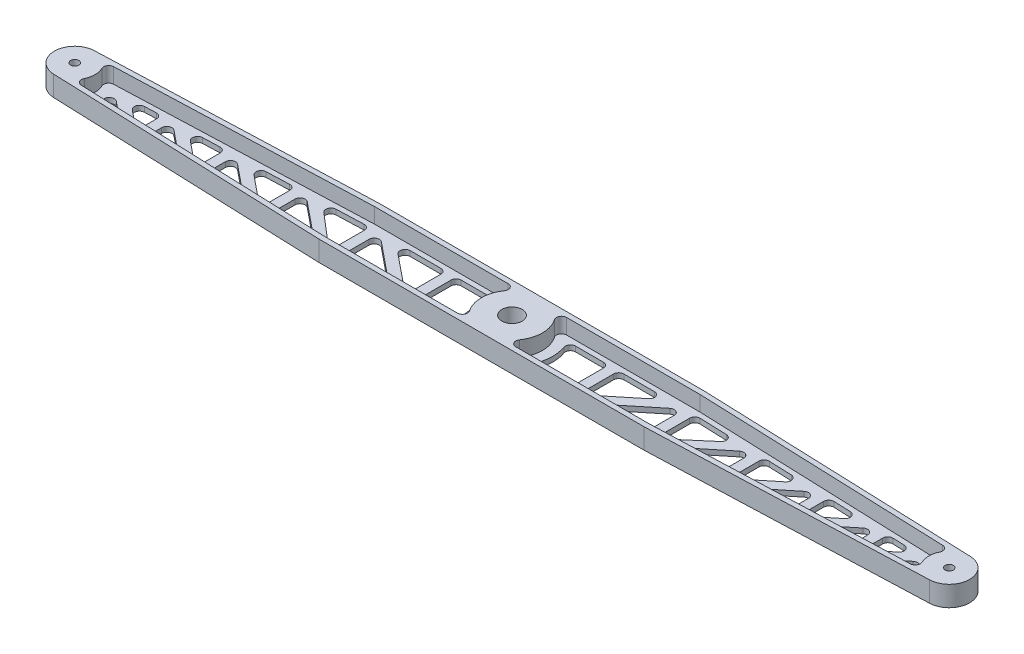
SolidWorks part; units mm, degrees
material "6061 Alloy"
ref_plane "Front Plane" through (0, 0, 0) normal (0, 0, 1) x (1, 0, 0)
ref_plane "Top Plane" through (0, 0, 0) normal (0, 1, 0) x (1, 0, 0)
ref_plane "Right Plane" through (0, 0, 0) normal (1, 0, 0) x (0, 0, -1)
sketch "Sketch1" plane through (0, 0, 0) normal (1, 0, 0) x (0, 0, -1)
  line L1 (-19.05, -6.35) -> (19.05, -6.35)
  line L2 (-19.05, -6.35) -> (-19.05, 6.35)
  line L3 (-19.05, 6.35) -> (19.05, 6.35)
  line L4 (19.05, -6.35) -> (19.05, 6.35)
  line L5 (-19.05, -6.35) -> (19.05, 6.35) construction
  line L6 (-19.05, 6.35) -> (19.05, -6.35) construction
  point P0 (0, 0)
  dimension "D1" = 38.1
  dimension "D2" = 12.7
extrude "Boss-Extrude1" add sketch "Sketch1" along normal mid plane 584.2
sketch "Sketch2" plane through (0, 6.35, 0) normal (0, 1, 0) x (1, 0, 0)
  circle A0 centre (0, 0) radius 6.35
  dimension "D1" = 12.7
extrude "Pivot Hole" cut sketch "Sketch2" against normal through all
hole_wizard "End Holes" positions "Sketch4" profile "Sketch3" tap size "1/4-20" standard "ANSI Inch" end condition through all
sketch "Sketch4" plane through (0, -6.35, 0) normal (0, -1, 0) x (-1, 0, 0)
  line L0 (273.05, 0) -> (292.1, 0) construction
  line L1 (292.1, -19.05) -> (292.1, 19.05) construction
  line L4 (-273.05, 0) -> (-292.1, 0) construction
  line L5 (-292.1, -19.05) -> (-292.1, 19.05) construction
  point P0 (273.05, 0)
  point P2 (-273.05, 0)
  dimension "D1" = 19.05
sketch "Sketch3" plane through (-273.05, -6.35, 0) normal (1, 0, 0) x (0, 0, -1)
  line L0 (0, 0) -> (0, 12.7)
  line L1 (0, 12.7) -> (2.5527, 12.7)
  line L2 (2.5527, 12.7) -> (2.5527, 0)
  line L5 (2.5527, 0) -> (0, 0)
  line L11 (0, -6.35) -> (0, 107.95) construction
  dimension "Thread Major Dia." = 5.1054
  dimension "Thru Tap Drill Depth" = 12.7
sketch "Sketch7" plane through (0, 6.35, 0) normal (0, 1, 0) x (1, 0, 0)
  line L0 (101.6, 19.05) -> (-101.6, 19.05)
  line L1 (292.1, 19.05) -> (-292.1, 19.05) construction
  line L2 (-101.6, 19.05) -> (-273.5194, 12.6913)
  line L3 (-273.5194, -12.6913) -> (-101.6, -19.05)
  line L4 (292.1, -19.05) -> (-292.1, -19.05) construction
  line L5 (-101.6, -19.05) -> (101.6, -19.05)
  line L6 (0, 19.05) -> (0, -19.05) construction
  line L7 (273.5194, -12.6913) -> (101.6, -19.05)
  line L8 (101.6, 19.05) -> (273.5194, 12.6913)
  line L13 (-292.1, 19.05) -> (-292.1, -19.05)
  line L14 (-292.1, -19.05) -> (292.1, -19.05)
  line L15 (292.1, -19.05) -> (292.1, 19.05)
  line L16 (292.1, 19.05) -> (-292.1, 19.05)
  line L17 (-292.1, 19.05) -> (-292.1, -19.05)
  line L18 (-292.1, -19.05) -> (292.1, -19.05)
  line L19 (292.1, -19.05) -> (292.1, 19.05)
  line L20 (292.1, 19.05) -> (-292.1, 19.05)
  arc A0 (-273.5194, 12.6913) -> (-273.5194, -12.6913) centre (-273.05, 0) ccw
  arc A1 (273.5194, 12.6913) -> (273.5194, -12.6913) centre (273.05, 0) cw
  line M4 (-292.1, 19.05) -> (-292.1, -19.05)
  line M5 (-292.1, -19.05) -> (292.1, -19.05)
  line M6 (292.1, -19.05) -> (292.1, 19.05)
  line M7 (292.1, 19.05) -> (-292.1, 19.05)
  dimension "D2" = 12.7
  dimension "D1" = 101.6
  dimension "D3" = 0
extrude "Cut-Extrude3" cut sketch "Sketch7" against normal up to next contours A0 L2 L3 M7 M4 M5 | L8 A1 L7 M5 M6 M7 region at (196.85, 6.35, -17.1073) region at (-187.6315, 6.35, -17.8121)
sketch "Sketch9" plane through (0, 6.35, 0) normal (0, 1, 0) x (1, 0, 0)
  line L0 (-265.0075, 9.829) -> (-101.6, 15.8728)
  line L1 (-101.6, 15.8728) -> (-10.5336, 15.8728)
  line L2 (-10.5336, -15.8728) -> (-101.6, -15.8728)
  line L3 (-101.6, -15.8728) -> (-265.0075, -9.829)
  line L4 (-273.5194, -12.6913) -> (-101.6, -19.05) construction
  line L5 (-101.6, 19.05) -> (-273.5194, 12.6913) construction
  line L6 (0, 0) -> (0, -19.05) construction
  line L7 (101.6, -19.05) -> (-101.6, -19.05) construction
  line L8 (101.6, -15.8728) -> (265.0075, -9.829)
  line L9 (10.5336, -15.8728) -> (101.6, -15.8728)
  line L10 (101.6, 15.8728) -> (10.5336, 15.8728)
  line L11 (265.0075, 9.829) -> (101.6, 15.8728)
  arc A0 (-265.0075, 9.829) -> (-265.0075, -9.829) centre (-273.05, 0) cw
  arc A1 (-273.5194, 12.6913) -> (-273.5194, -12.6913) centre (-273.05, 0) ccw construction
  arc A2 (-10.5336, 15.8728) -> (-10.5336, -15.8728) centre (0, 0) ccw
  arc A3 (10.5336, 15.8728) -> (10.5336, -15.8728) centre (0, 0) cw
  arc A4 (265.0075, 9.829) -> (265.0075, -9.829) centre (273.05, 0) ccw
  dimension "D3" = 19.05
  dimension "D1" = 3.175
  dimension "D2" = 3.175
extrude "Cut-Extrude4" cut sketch "Sketch9" against normal blind 9.525
sketch "Sketch10" plane through (0, -3.175, 0) normal (0, 1, 0) x (1, 0, 0)
  line L0 (-130.0551, 11.6432) -> (-101.6, 12.6957)
  line L1 (-101.6, 12.6957) -> (-101.6, -12.6957)
  line L2 (-101.6, -12.6957) -> (-130.0551, 11.6432)
  line L3 (-140.1121, 11.2712) -> (-111.0553, -12.3459)
  line L4 (-111.0553, -12.3459) -> (-140.1121, -11.2712)
  line L5 (-125.5837, -0.5374) -> (-121.4562, 4.2882) construction
  line L6 (-95.25, 12.6957) -> (-95.25, -12.6957)
  line L7 (-95.25, -12.6957) -> (-64.0104, -12.6957)
  line L8 (-64.0104, -12.6957) -> (-95.25, 12.6957)
  line L9 (-85.1823, 12.6957) -> (-53.9426, -12.6957)
  line L10 (-53.9426, -12.6957) -> (-53.9426, 12.6957)
  line L11 (-53.9426, 12.6957) -> (-85.1823, 12.6957)
  line L12 (-255.3365, 7.0095) -> (-101.6, 12.6957) construction
  line L13 (-101.6, 12.6957) -> (-21.9996, 12.6957) construction
  line L14 (-21.9996, -12.6957) -> (-101.6, -12.6957) construction
  line L15 (-101.6, -12.6957) -> (-255.3365, -7.0095) construction
  line L16 (-265.0075, -9.829) -> (-101.6, -15.8728) construction
  line L17 (-101.6, 15.8728) -> (-265.0075, 9.829) construction
  line L18 (-10.5336, 15.8728) -> (-101.6, 15.8728) construction
  line L19 (-101.6, -15.8728) -> (-10.5336, -15.8728) construction
  line L20 (-255.3365, 7.0095) -> (-237.2662, -7.6779)
  line L21 (-237.2662, -7.6779) -> (-255.3365, -7.0095)
  line L22 (-245.7069, 7.3657) -> (-226.7185, -8.068)
  line L23 (-226.7185, -8.068) -> (-226.7185, 8.068)
  line L24 (-226.7185, 8.068) -> (-245.7069, 7.3657)
  line L25 (-220.3685, 8.3028) -> (-220.3685, -8.3028)
  line L26 (-220.3685, -8.3028) -> (-198.9641, -9.0945)
  line L27 (-198.9641, -9.0945) -> (-220.3685, 8.3028)
  line L28 (-210.739, 8.659) -> (-188.4164, -9.4846)
  line L29 (-188.4164, -9.4846) -> (-188.4164, 9.4846)
  line L30 (-188.4164, 9.4846) -> (-210.739, 8.659)
  line L31 (-182.0664, 9.7195) -> (-182.0664, -9.7195)
  line L32 (-182.0664, -9.7195) -> (-157.0098, -10.6462)
  line L33 (-157.0098, -10.6462) -> (-182.0664, 9.7195)
  line L34 (-246.3013, -0.3342) -> (-242.2962, 4.5934) construction
  line L35 (-209.6663, -0.3958) -> (-205.6612, 4.5318) construction
  line L36 (-172.4369, 10.0757) -> (-146.4621, -11.0364)
  line L37 (-146.4621, -11.0364) -> (-146.4621, 11.0364)
  line L38 (-146.4621, 11.0364) -> (-172.4369, 10.0757)
  line L39 (-140.1121, 11.2712) -> (-140.1121, -11.2712)
  line L40 (-47.5926, 12.6957) -> (-47.5926, -12.6957)
  line L41 (-47.5926, -12.6957) -> (-21.9996, -12.6957)
  line L42 (-169.5381, -0.4634) -> (-165.533, 4.4642) construction
  line L43 (-21.9996, 12.6957) -> (-47.5926, 12.6957)
  line L44 (0, 0) -> (0, 19.05) construction
  line L45 (-79.6302, 0) -> (-75.6251, 4.9276) construction
  line L46 (101.6, 19.05) -> (-101.6, 19.05) construction
  arc A6 (-255.3365, 7.0095) -> (-255.3365, -7.0095) centre (-273.05, 0) cw
  arc A7 (-265.0075, -9.829) -> (-265.0075, 9.829) centre (-273.05, 0) ccw construction
  arc A8 (-21.9996, 12.6957) -> (-21.9996, -12.6957) centre (0, 0) ccw
  arc A9 (-10.5336, 15.8728) -> (-10.5336, -15.8728) centre (0, 0) ccw construction
  dimension "D3" = 6.35
  dimension "D4" = 6.35
  dimension "D1" = 3.175
  dimension "D2" = 3.175
  dimension "D5" = 6.35
  dimension "D6" = 6.35
  dimension "D7" = 6.35
  dimension "D8" = 6.35
  dimension "D9" = 6.35
  dimension "D10" = 6.35
extrude "Cut-Extrude5" cut sketch "Sketch10" against normal up to next
fillet "Fillet3" radius 3.175 34 edges at (-21.9996, -4.7625, 12.6957) (-21.9996, -4.7625, -12.6957) (-47.5926, -4.7625, -12.6957) (-47.5926, -4.7625, 12.6957) (-53.9426, -4.7625, 12.6957) (-53.9426, -4.7625, -12.6957) (-85.1823, -4.7625, -12.6957) (-64.0104, -4.7625, 12.6957) (-95.25, -4.7625, -12.6957) (-95.25, -4.7625, 12.6957) (-101.6, -4.7625, 12.6957) (-130.0551, -4.7625, -11.6432) (-101.6, -4.7625, -12.6957) (-111.0553, -4.7625, 12.3459) (-140.1121, -4.7625, -11.2712) (-140.1121, -4.7625, 11.2712) (-146.4621, -4.7625, 11.0364) (-146.4621, -4.7625, -11.0364) (-172.4369, -4.7625, -10.0757) (-157.0098, -4.7625, 10.6462) (-182.0664, -4.7625, -9.7195) (-182.0664, -4.7625, 9.7195) (-188.4164, -4.7625, 9.4846) (-188.4164, -4.7625, -9.4846) (-210.739, -4.7625, -8.659) (-198.9641, -4.7625, 9.0945) (-220.3685, -4.7625, -8.3028) (-220.3685, -4.7625, 8.3028) (-226.7185, -4.7625, 8.068) (-226.7185, -4.7625, -8.068) (-245.7069, -4.7625, -7.3657) (-237.2662, -4.7625, 7.6779) (-255.3365, -4.7625, 7.0095) (-255.3365, -4.7625, -7.0095)
mirror "Mirror1" about plane through (0, 0, 0) normal (1, 0, 0) of "Fillet3", "Cut-Extrude5"
fillet "Fillet4" radius 3.175 8 edges at (10.5336, 1.5875, 15.8728) (10.5336, 1.5875, -15.8728) (265.0075, 1.5875, 9.829) (265.0075, 1.5875, -9.829) (-265.0075, 1.5875, 9.829) (-265.0075, 1.5875, -9.829) (-10.5336, 1.5875, 15.8728) (-10.5336, 1.5875, -15.8728)
